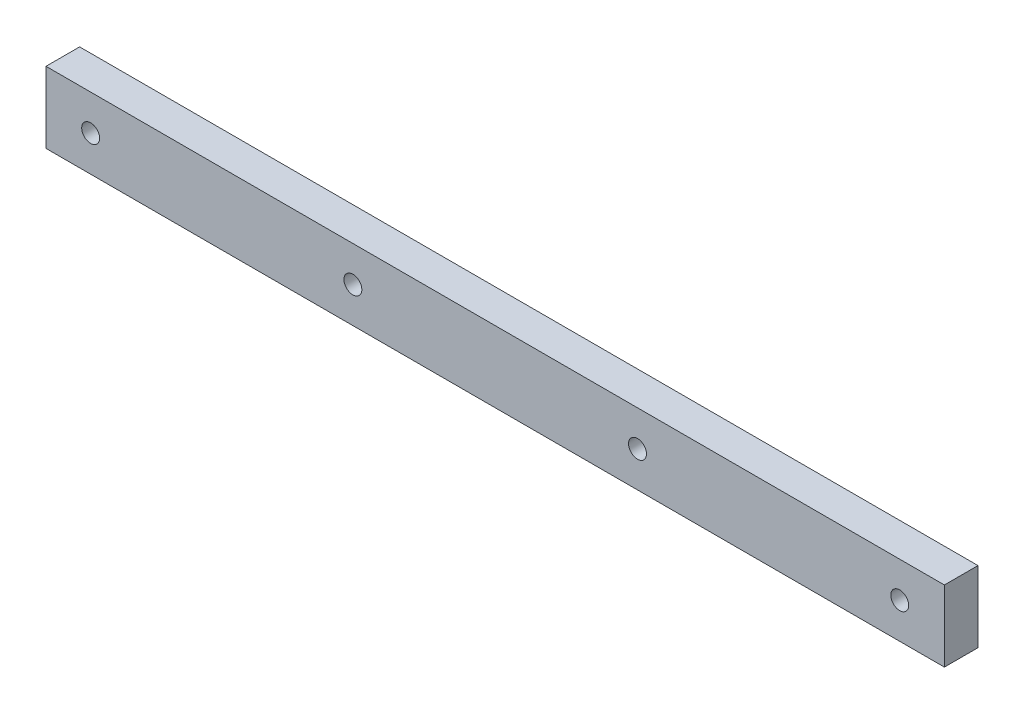
SolidWorks part; units mm, degrees
ref_plane "Front Plane" through (0, 0, 0) normal (0, 0, 1) x (1, 0, 0)
ref_plane "Top Plane" through (0, 0, 0) normal (0, 1, 0) x (1, 0, 0)
ref_plane "Right Plane" through (0, 0, 0) normal (1, 0, 0) x (0, 0, -1)
sketch "Sketch1" plane through (0, 0, 0) normal (0, 0, 1) x (1, 0, 0)
  line L0 (-80.17, 0) -> (80.17, 0)
  line L1 (80.17, 0) -> (80.17, 12.7)
  line L2 (80.17, 12.7) -> (-80.17, 12.7)
  line L3 (-80.17, 12.7) -> (-80.17, 0)
  circle A0 centre (-72.2, 6.35) radius 1.6
  circle A1 centre (72.2, 6.35) radius 1.6
  circle A2 centre (-25.4, 6.35) radius 1.6
  circle A3 centre (25.4, 6.35) radius 1.6
extrude "Boss-Extrude1" add sketch "Sketch1" along normal blind 6
ref_plane "Piv_R_px" through (-72.2, 0, 0) normal (1, 0, 0) x (0, 0, -1)
ref_plane "Piv_R_py" through (0, 6.35, 0) normal (0, 1, 0) x (1, 0, 0)
ref_axis "Piv_R" through (-72.2, 6.35, 6.3) along (0, 0, -1)
ref_plane "Piv_L_px" through (72.2, 0, 0) normal (1, 0, 0) x (0, 0, -1)
ref_plane "Piv_L_py" through (0, 6.35, 0) normal (0, 1, 0) x (1, 0, 0)
ref_axis "Piv_L" through (72.2, 6.35, 6.3) along (0, 0, -1)
ref_plane "Mid_R" through (0, 0, 13.5) normal (0, 0, 1) x (1, 0, 0)
ref_plane "Mid_L" through (0, 0, 7.5) normal (0, 0, 1) x (1, 0, 0)
